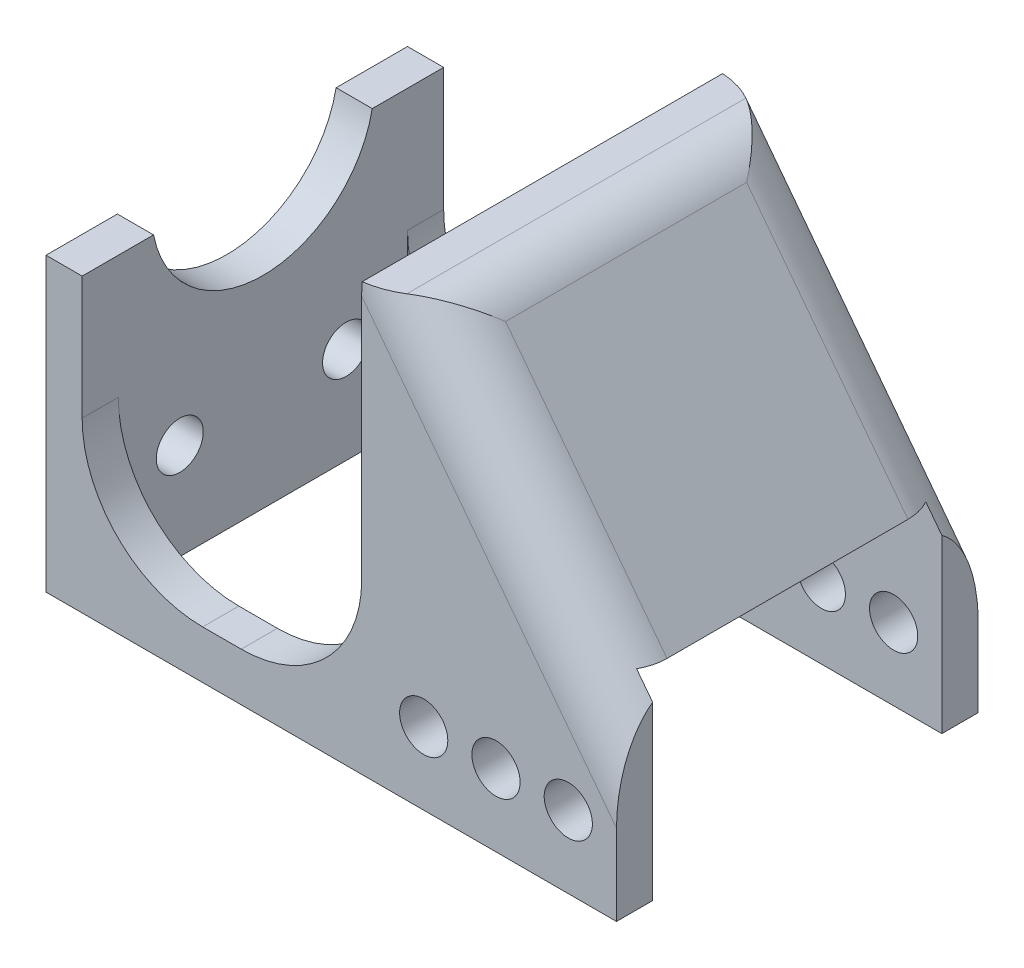
SolidWorks part; units mm, degrees
ref_plane "Front Plane" through (0, 0, 0) normal (0, 0, 1) x (1, 0, 0)
ref_plane "Top Plane" through (0, 0, 0) normal (0, 1, 0) x (1, 0, 0)
ref_plane "Right Plane" through (0, 0, 0) normal (1, 0, 0) x (0, 0, -1)
sketch "Sketch1" plane through (0, 0, 0) normal (0, 0, 1) x (1, 0, 0)
  line L0 (0, 0) -> (-10, -13.0323) construction
  line L1 (0, 0) -> (10, -13.0323) construction
  line L2 (-10, -13.0323) -> (10, -13.0323)
  line L9 (-11.1437, 22.3593) -> (-5.7608, 22.5296)
  line L10 (-11.1437, -9.0323) -> (-11.1437, 22.3593)
  line L11 (10, 1.9125) -> (10, -13.0323)
  line L12 (-5.7608, 22.5296) -> (10, 1.9125)
  line L13 (-10, -13.0323) -> (-37.3437, -13.0323)
  line L14 (-37.3437, -13.0323) -> (-37.3437, 11.1805)
  line L15 (-37.3437, 11.1805) -> (-34.3437, 11.1805)
  line L16 (-34.3437, 11.1805) -> (-34.3437, -9.0323)
  line L17 (-11.1437, -9.0323) -> (-34.3437, -9.0323)
  circle A2 centre (0, -7.0323) radius 2
  circle A3 centre (6, -7.0323) radius 2
  circle A4 centre (-6, -7.0323) radius 2
  dimension "D6" = 4
  dimension "D7" = 4
  dimension "D10" = 4
  dimension "D1" = 75
  dimension "D2" = 20
  dimension "D3" = 35.41
  dimension "D4" = 23.2
  dimension "D5" = 6
  dimension "D8" = 6
  dimension "D9" = 6
  dimension "D11" = 3
  dimension "D12" = 4
extrude "Boss-Extrude1" add sketch "Sketch1" along normal blind 30
sketch "Sketch2" plane through (10, 0, 0) normal (1, 0, 0) x (0, 0, -1)
  line L1 (-27, -13.0323) -> (-3, -13.0323)
  line L2 (-27, -13.0323) -> (-27, 2.9677)
  line L3 (-27, 2.9677) -> (-3, 2.9677)
  line L4 (-3, -13.0323) -> (-3, 2.9677)
  line L5 (-30, -13.0323) -> (0, -13.0323) construction
  dimension "D1" = 16
extrude "Cut-Extrude1" cut sketch "Sketch2" against normal up to surface (44.3437 mm away) up to face at (-34.3437, 1.0741, 15)
sketch "Sketch3" plane through (-11.1437, 0, 0) normal (-1, 0, 0) x (0, 0, 1)
  line L0 (3, 2.9677) -> (27, 2.9677) construction
  circle A0 centre (15, 12.9677) radius 9
  circle A1 centre (15, 12.9677) radius 6 construction
  circle A2 centre (15, 18.9677) radius 2
  circle A3 centre (15, 6.9677) radius 2
  circle A4 centre (9, 12.9677) radius 2
  circle A5 centre (21, 12.9677) radius 2
  point P5 (15, 2.9677)
  dimension "D1" = 18
  dimension "D2" = 10
  dimension "D3" = 12
  dimension "D4" = 4
  dimension "D5" = 4
  dimension "D6" = 4
  dimension "D7" = 4
extrude "Cut-Extrude2" cut sketch "Sketch3" against normal blind 3
fillet "Fillet1" [suppressed] radius 2
sketch "Sketch4" plane through (-34.3437, 0, 0) normal (1, 0, 0) x (0, 0, -1)
  circle A0 centre (-15, 12.9677) radius 2 construction
  arc A1 (-17, 12.9677) -> (-13, 12.9677) centre (-15, 12.9677) ccw construction
  arc A2 (-17, 12.9677) -> (-13, 12.9677) centre (-15, 12.9677) ccw construction
  circle A3 centre (-15, 12.9677) radius 9.25
  dimension "D1" = 4
  dimension "D2" = 18.5
extrude "Cut-Extrude3" cut sketch "Sketch4" against normal through all
fillet "Fillet2" radius 10 4 edges at (-11.1437, -9.0323, 1.5) (-11.1437, -9.0323, 28.5) (-34.3437, -9.0323, 28.5) (-34.3437, -9.0323, 1.5)
fillet "Fillet3" radius 5 3 edges at (-5.7608, 22.5296, 15) (2.1196, 12.2211, 30) (2.1196, 12.2211, 0)
hole_wizard "M3.5 Clearance Hole1" positions "Sketch5" profile "Sketch6" hole size "M3.5" standard "ANSI Metric" end condition through all
sketch "Sketch5" plane through (-37.3437, 0, 0) normal (-1, 0, 0) x (0, 0, 1)
  point P0 (8.1, -5.0323)
  point P3 (21.9, -5.0323)
sketch "Sketch6" plane through (-37.3437, -5.0323, 8.1) normal (0, 1, 0) x (0, 0, 1)
  line L0 (0, 0) -> (0, 47.3437)
  line L1 (0, 47.3437) -> (1.95, 47.3437)
  line L2 (1.95, 47.3437) -> (1.95, 0.025)
  line L3 (1.95, 0.025) -> (1.975, 0)
  line L5 (1.975, 0) -> (0, 0)
  line L6 (-1.95, 0.025) -> (-1.975, 0) construction
  line L11 (0, -6.35) -> (0, 107.95) construction
  dimension "Thru Hole Dia." = 3.9
  dimension "Thru Hole Depth" = 47.3437
  dimension "Near C'Sink Dia." = 3.95
  dimension "Near C'Sink Angle" = 90
